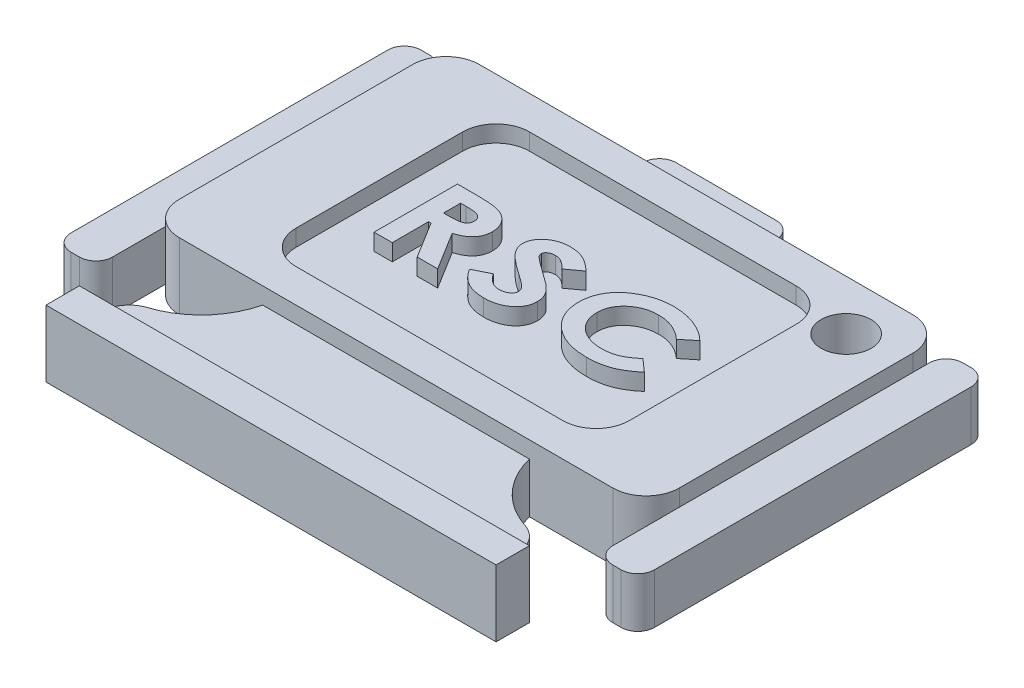
SolidWorks part; units mm, degrees
ref_plane "Piano frontale" through (0, 0, 0) normal (0, 0, 1) x (1, 0, 0)
ref_plane "Piano superiore" through (0, 0, 0) normal (0, 1, 0) x (1, 0, 0)
ref_plane "Piano destro" through (0, 0, 0) normal (1, 0, 0) x (0, 0, -1)
sketch "Schizzo1" plane through (0, 0, 0) normal (0, 1, 0) x (1, 0, 0)
  line L1 (-12.1301, 10.3282) -> (13.8699, 10.3282)
  line L2 (-14.1301, 8.3282) -> (-14.1301, -5.6718)
  line L3 (-12.1301, -7.6718) -> (13.8699, -7.6718)
  line L4 (15.8699, 8.3282) -> (15.8699, -5.6718)
  line L5 (-3.1301, 10.3282) -> (4.8699, 10.3282)
  line L6 (-3.1301, 10.3282) -> (-3.1301, 11.1282)
  line L7 (-2.1301, 12.1282) -> (3.8699, 12.1282)
  line L8 (4.8699, 10.3282) -> (4.8699, 11.1282)
  line L9 (-15.6301, 10.3282) -> (-15.1301, 10.3282)
  line L10 (-16.6301, 9.3282) -> (-16.6301, -9.6718)
  line L11 (-15.6301, -10.6718) -> (-15.1301, -10.6718)
  line L12 (-14.1301, 9.3282) -> (-14.1301, -9.6718)
  line L13 (16.8699, 10.3282) -> (17.3699, 10.3282)
  line L14 (15.8699, 9.3282) -> (15.8699, -9.6718)
  line L15 (16.8699, -10.6718) -> (17.3699, -10.6718)
  line L16 (18.3699, 9.3282) -> (18.3699, -9.6718)
  line L17 (-12.6301, -13.1718) -> (14.3699, -13.1718)
  line L18 (-12.6301, -13.1718) -> (-12.6301, -15.1718)
  line L19 (-12.6301, -15.1718) -> (14.3699, -15.1718)
  line L20 (14.3699, -13.1718) -> (14.3699, -15.1718)
  line L21 (-7.1301, -7.6718) -> (8.8699, -7.6718)
  line L25 (-11.6301, -13.1718) -> (12.4966, -13.1718)
  line L26 (-7.1301, -7.6718) -> (8.8699, -7.6718)
  line L27 (-7.1301, -7.6718) -> (-7.1301, -13.1718)
  line L28 (-7.1301, -13.1718) -> (8.8699, -13.1718)
  line L29 (8.8699, -7.6718) -> (8.8699, -13.1718)
  line L30 (-7.1301, -13.1718) -> (-11.6301, -13.1718)
  line L31 (-7.1301, -13.1718) -> (-7.1301, -11.1718)
  line L32 (-7.1301, -11.1718) -> (-9.9301, -11.1718)
  line L33 (-11.6301, -13.1718) -> (-11.6301, -12.8718)
  line L34 (8.8699, -13.1718) -> (13.3699, -13.1718)
  line L35 (8.8699, -13.1718) -> (8.8699, -11.1718)
  line L36 (8.8699, -11.1718) -> (11.6699, -11.1718)
  line L37 (13.3699, -13.1718) -> (13.3699, -12.8718)
  line L38 (-7.1301, 8.3282) -> (8.8699, 8.3282)
  line L39 (-9.1301, 6.3282) -> (-9.1301, -3.6718)
  line L40 (-7.1301, -5.6718) -> (8.8699, -5.6718)
  line L41 (10.8699, 6.3282) -> (10.8699, -3.6718)
  arc A0 (13.8699, -7.6718) -> (15.8699, -5.6718) centre (13.8699, -5.6718) ccw
  arc A1 (-14.1301, -5.6718) -> (-12.1301, -7.6718) centre (-12.1301, -5.6718) ccw
  arc A2 (-9.1301, -3.6718) -> (-7.1301, -5.6718) centre (-7.1301, -3.6718) ccw
  arc A3 (8.8699, -5.6718) -> (10.8699, -3.6718) centre (8.8699, -3.6718) ccw
  arc A4 (8.8699, 8.3282) -> (10.8699, 6.3282) centre (8.8699, 6.3282) cw
  arc A5 (-7.1301, 8.3282) -> (-9.1301, 6.3282) centre (-7.1301, 6.3282) ccw
  arc A6 (-12.1301, 10.3282) -> (-14.1301, 8.3282) centre (-12.1301, 8.3282) ccw
  arc A7 (13.8699, 10.3282) -> (15.8699, 8.3282) centre (13.8699, 8.3282) cw
  arc A8 (17.3699, -10.6718) -> (18.3699, -9.6718) centre (17.3699, -9.6718) ccw
  arc A9 (17.3699, 10.3282) -> (18.3699, 9.3282) centre (17.3699, 9.3282) cw
  arc A10 (16.8699, 10.3282) -> (15.8699, 9.3282) centre (16.8699, 9.3282) ccw
  arc A11 (15.8699, -9.6718) -> (16.8699, -10.6718) centre (16.8699, -9.6718) ccw
  arc A12 (-15.1301, -10.6718) -> (-14.1301, -9.6718) centre (-15.1301, -9.6718) ccw
  arc A13 (-16.6301, -9.6718) -> (-15.6301, -10.6718) centre (-15.6301, -9.6718) ccw
  arc A14 (-15.1301, 10.3282) -> (-14.1301, 9.3282) centre (-15.1301, 9.3282) cw
  arc A15 (-15.6301, 10.3282) -> (-16.6301, 9.3282) centre (-15.6301, 9.3282) ccw
  arc A16 (3.8699, 12.1282) -> (4.8699, 11.1282) centre (3.8699, 11.1282) cw
  arc A17 (-3.1301, 11.1282) -> (-2.1301, 12.1282) centre (-2.1301, 11.1282) cw
  arc A18 (11.6699, -11.1718) -> (13.3699, -12.8718) centre (11.6699, -12.8718) cw
  arc A19 (-9.9301, -11.1718) -> (-11.6301, -12.8718) centre (-9.9301, -12.8718) ccw
  point P51 (-14.1301, 10.3282)
  point P54 (15.8699, 10.3282)
  point P57 (18.3699, -10.6718)
  point P60 (18.3699, 10.3282)
  point P63 (15.8699, 10.3282)
  point P70 (-16.6301, -10.6718)
  point P73 (-14.1301, 10.3282)
  point P76 (-16.6301, 10.3282)
  point P79 (4.8699, 12.1282)
  point P82 (-3.1301, 12.1282)
  point P85 (13.3699, -11.1718)
  point P88 (-11.6301, -11.1718)
  dimension "D24" = 2
  dimension "D25" = 1
  dimension "D26" = 1.7
  dimension "D1" = 30
  dimension "D2" = 1.8
  dimension "D3" = 8
  dimension "D4" = 11
  dimension "D5" = 21
  dimension "D6" = 21
  dimension "D7" = 0
  dimension "D8" = 0
  dimension "D9" = 2.5
  dimension "D10" = 2.5
  dimension "D11" = 27
  dimension "D12" = 1.5
  dimension "D13" = 5.5
  dimension "D14" = 2
  dimension "D15" = 2
  dimension "D16" = 18
  dimension "D17" = 2
  dimension "D18" = 1
  dimension "D19" = 1
  dimension "D20" = 2
  dimension "D21" = 2
  dimension "D22" = 5
  dimension "D23" = 5
extrude "Estrusione-Estrusione1" add sketch "Schizzo1" along normal blind 3 contours L9 A15 L10 A13 L11 A12 L12 L2 A14 | L14 A11 L15 A8 L16 A9 L13 A10 L4 | A17 L6 L1 L8 A16 L7 | L29 L3 L27 L25 | A18 L36 L29 L17 L37 | L32 A19 L33 L17 L27 region at (0.8699, 0, -11.2074) region at (-15.3801, 0, 0.1718) region at (17.1199, 0, 0.1718) region at (0.8699, 0, 10.4218) region at (-9.2417, 0, 12.2177) region at (10.9815, 0, 12.2177)
extrude "Estrusione-Estrusione2" add sketch "Schizzo1<3>" along normal blind 4 contours A7 L1 A6 L2 A1 L3 A0 L4 A5 L38 A4 L41 A3 L40 A2 L39 | L20 L17 L25 L18 L19 region at (-7.6301, 0, -9.9784) region at (0.8699, 0, 14.1718)
sketch "Schizzo1<3>" plane through (0, 0, 0) normal (0, 1, 0) x (1, 0, 0) same geometry as "Schizzo1"
extrude "Estrusione-Estrusione3" add sketch "Schizzo1<4>" along normal blind 3 contours L38 A5 L39 A2 L40 A3 L41 A4 region at (0.8699, 0, -1.3282)
sketch "Schizzo1<4>" plane through (0, 0, 0) normal (0, 1, 0) x (1, 0, 0) same geometry as "Schizzo1"
fillet "Raccordo1" radius 5 2 edges at (-7.1301, 1.5, 11.1718) (8.8699, 1.5, 11.1718)
sketch "Schizzo3" plane through (0, 4, 0) normal (0, 1, 0) x (1, 0, 0)
  line L0 (-12.1301, 10.3282) -> (13.8699, 10.3282) construction
  line L1 (15.8699, 8.3282) -> (15.8699, -5.6718) construction
  circle A0 centre (12.8699, 7.3282) radius 1.5
  dimension "D1" = 3
  dimension "D2" = 3
  dimension "D3" = 3
extrude "Taglio-Estrusione1" cut sketch "Schizzo3" against normal through all
sketch "Schizzo4" plane through (0, 3, 0) normal (0, 1, 0) x (1, 0, 0)
  text T0 "RSC" font "Yu Gothic" height 5
extrude "Taglio-Estrusione3" [suppressed] cut sketch "Schizzo4" against normal blind 1
sketch "Schizzo5" plane through (0, 3, 0) normal (0, 1, 0) x (1, 0, 0)
  text T0 "RSC" font "Century Gothic" height 5
extrude "Taglio-Estrusione4" [suppressed] cut sketch "Schizzo5" against normal blind 1
extrude "Estrusione-Estrusione4" add sketch "Schizzo5<2>" along normal blind 1
sketch "Schizzo5<2>" plane through (0, 3, 0) normal (0, 1, 0) x (1, 0, 0) same geometry as "Schizzo5"
